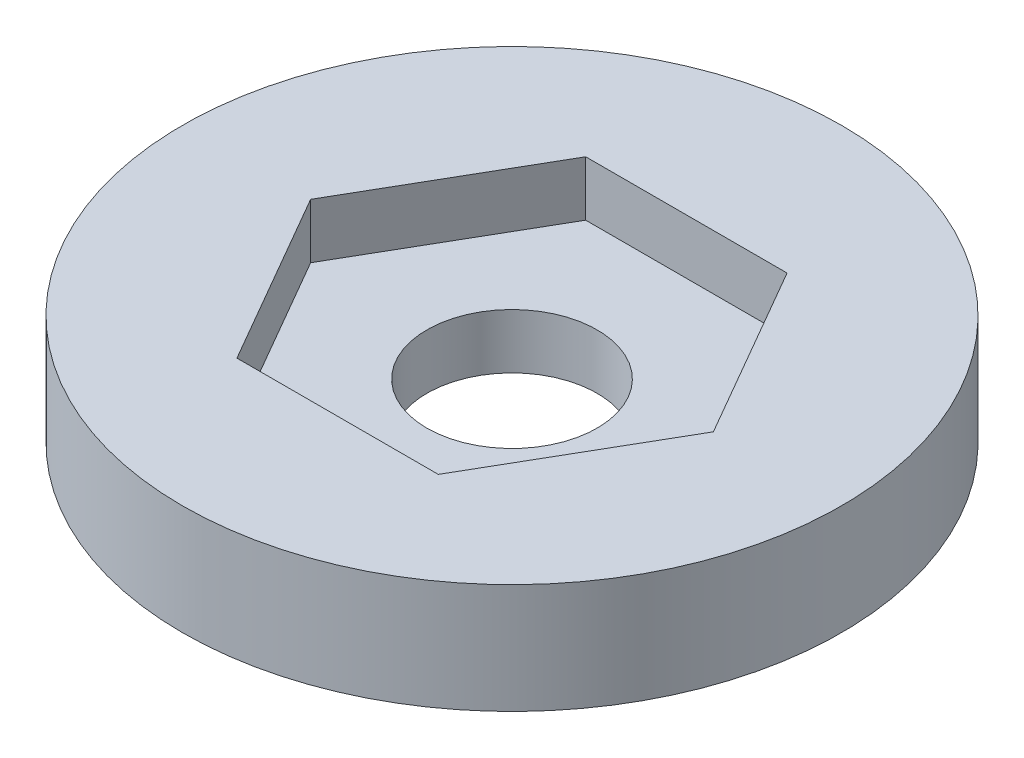
SolidWorks part; units mm, degrees
ref_plane "Front Plane" through (0, 0, 0) normal (0, 0, 1) x (1, 0, 0)
ref_plane "Top Plane" through (0, 0, 0) normal (0, 1, 0) x (1, 0, 0)
ref_plane "Right Plane" through (0, 0, 0) normal (1, 0, 0) x (0, 0, -1)
sketch "Sketch1" plane through (0, 0, 0) normal (0, 1, 0) x (1, 0, 0)
  circle A0 centre (0, 0) radius 3.1
  circle A1 centre (0, 0) radius 12
  dimension "D1" = 6.2
  dimension "D2" = 24
extrude "Boss-Extrude1" add sketch "Sketch1" along normal blind 4
sketch "Sketch2" plane through (0, 4, 0) normal (0, 1, 0) x (1, 0, 0)
  line L1 (7.3323, 0) -> (3.6662, 6.35)
  line L2 (3.6662, 6.35) -> (-3.6662, 6.35)
  line L3 (-3.6662, 6.35) -> (-7.3323, 0)
  line L4 (-7.3323, 0) -> (-3.6662, -6.35)
  line L5 (-3.6662, -6.35) -> (3.6662, -6.35)
  line L6 (3.6662, -6.35) -> (7.3323, 0)
  circle A0 centre (0, 0) radius 6.35 construction
  dimension "D1" = 12.7
extrude "Cut-Extrude1" cut sketch "Sketch2" against normal blind 2
